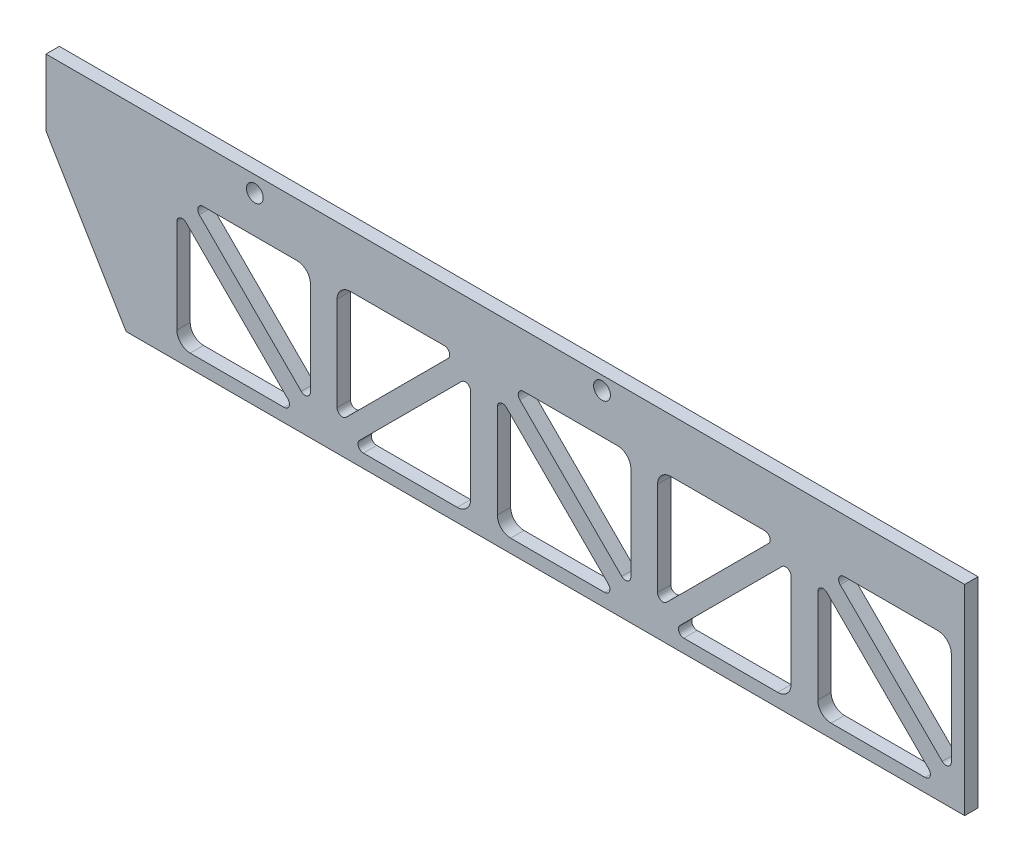
SolidWorks part; units mm, degrees
material "Pine"
ref_plane "Front Plane" through (0, 0, 0) normal (0, 0, 1) x (1, 0, 0)
ref_plane "Top Plane" through (0, 0, 0) normal (0, 1, 0) x (1, 0, 0)
ref_plane "Right Plane" through (0, 0, 0) normal (1, 0, 0) x (0, 0, -1)
sketch "Model" plane through (0, 0, 0) normal (0, 0, 1) x (1, 0, 0)
  line L8 (-171.2321, 6.35) -> (-215.9, 6.35)
  line L9 (-222.25, 57.3679) -> (-222.25, 12.7)
  line L10 (-217.9139, 59.1639) -> (-169.4361, 10.6861)
  line L11 (-234.95, 57.3679) -> (-234.95, 12.7)
  line L12 (-241.3, 6.35) -> (-285.9679, 6.35)
  line L13 (-239.2861, 59.1639) -> (-287.7639, 10.6861)
  line L14 (-294.1139, 17.0361) -> (-245.6361, 65.5139)
  line L15 (-298.45, 63.5) -> (-298.45, 18.8321)
  line L16 (-247.4321, 69.85) -> (-292.1, 69.85)
  line L17 (-323.6321, 6.35) -> (-368.3, 6.35)
  line L18 (-374.65, 57.3679) -> (-374.65, 12.7)
  line L19 (-370.3139, 59.1639) -> (-321.8361, 10.6861)
  line L20 (-18.8321, 6.35) -> (-63.5, 6.35)
  line L21 (-69.85, 57.3679) -> (-69.85, 12.7)
  line L22 (-17.0361, 10.6861) -> (-65.5139, 59.1639)
  line L23 (-82.55, 57.3679) -> (-82.55, 12.7)
  line L24 (-88.9, 6.35) -> (-133.5679, 6.35)
  line L25 (-86.8861, 59.1639) -> (-135.3639, 10.6861)
  line L26 (-93.2361, 65.5139) -> (-141.7139, 17.0361)
  line L27 (-146.05, 63.5) -> (-146.05, 18.8321)
  line L28 (-95.0321, 69.85) -> (-139.7, 69.85)
  line L29 (-163.0861, 17.0361) -> (-211.5639, 65.5139)
  line L30 (-165.1, 69.85) -> (-209.7679, 69.85)
  line L31 (-158.75, 63.5) -> (-158.75, 18.8321)
  line L32 (-315.4861, 17.0361) -> (-363.9639, 65.5139)
  line L33 (-317.5, 69.85) -> (-362.1679, 69.85)
  line L34 (-311.15, 63.5) -> (-311.15, 18.8321)
  line L35 (-398.78, 0) -> (-436.88, 63.5)
  line L36 (0, 0) -> (-398.78, 0)
  line L37 (0, 0) -> (0, 95.25)
  line L38 (0, 95.25) -> (-436.88, 95.25)
  line L39 (-436.88, 63.5) -> (-436.88, 95.25)
  line L40 (-6.35, 63.5) -> (-6.35, 18.8321)
  line L41 (-59.1639, 65.5139) -> (-10.6861, 17.0361)
  line L42 (-12.7, 69.85) -> (-57.3679, 69.85)
  arc A0 (-222.25, 12.7) -> (-215.9, 6.35) centre (-215.9, 12.7) ccw
  arc A1 (-217.9139, 59.1639) -> (-222.25, 57.3679) centre (-219.71, 57.3679) ccw
  arc A2 (-171.2321, 6.35) -> (-169.4361, 10.6861) centre (-171.2321, 8.89) ccw
  arc A3 (-234.95, 57.3679) -> (-239.2861, 59.1639) centre (-237.49, 57.3679) ccw
  arc A4 (-241.3, 6.35) -> (-234.95, 12.7) centre (-241.3, 12.7) ccw
  arc A5 (-287.7639, 10.6861) -> (-285.9679, 6.35) centre (-285.9679, 8.89) ccw
  arc A6 (-245.6361, 65.5139) -> (-247.4321, 69.85) centre (-247.4321, 67.31) ccw
  arc A7 (-298.45, 18.8321) -> (-294.1139, 17.0361) centre (-295.91, 18.8321) ccw
  arc A8 (-292.1, 69.85) -> (-298.45, 63.5) centre (-292.1, 63.5) ccw
  arc A9 (-323.6321, 6.35) -> (-321.8361, 10.6861) centre (-323.6321, 8.89) ccw
  arc A10 (-374.65, 12.7) -> (-368.3, 6.35) centre (-368.3, 12.7) ccw
  arc A11 (-370.3139, 59.1639) -> (-374.65, 57.3679) centre (-372.11, 57.3679) ccw
  arc A12 (-69.85, 12.7) -> (-63.5, 6.35) centre (-63.5, 12.7) ccw
  arc A13 (-65.5139, 59.1639) -> (-69.85, 57.3679) centre (-67.31, 57.3679) ccw
  arc A14 (-18.8321, 6.35) -> (-17.0361, 10.6861) centre (-18.8321, 8.89) ccw
  arc A15 (-82.55, 57.3679) -> (-86.8861, 59.1639) centre (-85.09, 57.3679) ccw
  arc A16 (-88.9, 6.35) -> (-82.55, 12.7) centre (-88.9, 12.7) ccw
  arc A17 (-135.3639, 10.6861) -> (-133.5679, 6.35) centre (-133.5679, 8.89) ccw
  arc A18 (-93.2361, 65.5139) -> (-95.0321, 69.85) centre (-95.0321, 67.31) ccw
  arc A19 (-146.05, 18.8321) -> (-141.7139, 17.0361) centre (-143.51, 18.8321) ccw
  arc A20 (-139.7, 69.85) -> (-146.05, 63.5) centre (-139.7, 63.5) ccw
  arc A21 (-163.0861, 17.0361) -> (-158.75, 18.8321) centre (-161.29, 18.8321) ccw
  arc A22 (-209.7679, 69.85) -> (-211.5639, 65.5139) centre (-209.7679, 67.31) ccw
  arc A23 (-158.75, 63.5) -> (-165.1, 69.85) centre (-165.1, 63.5) ccw
  arc A24 (-362.1679, 69.85) -> (-363.9639, 65.5139) centre (-362.1679, 67.31) ccw
  arc A25 (-311.15, 63.5) -> (-317.5, 69.85) centre (-317.5, 63.5) ccw
  arc A26 (-315.4861, 17.0361) -> (-311.15, 18.8321) centre (-313.69, 18.8321) ccw
  arc A27 (-10.6861, 17.0361) -> (-6.35, 18.8321) centre (-8.89, 18.8321) ccw
  arc A28 (-57.3679, 69.85) -> (-59.1639, 65.5139) centre (-57.3679, 67.31) ccw
  arc A29 (-6.35, 63.5) -> (-12.7, 69.85) centre (-12.7, 63.5) ccw
  circle A30 centre (-172.466, 88.9) radius 4
  circle A31 centre (-337.566, 87.63) radius 4
  dimension "D2" = 172.466
  dimension "D4" = 8
  dimension "D5" = 165.1
  dimension "D7" = 8
  dimension "D1" = 95.25
  dimension "D3" = 6.35
  dimension "D6" = 7.62
extrude "Boss-Extrude1" add sketch "Model" along normal blind 6.35
equation "\"thick\"=0.25"
equation "\"D1@Boss-Extrude1\"=\"thick\""
